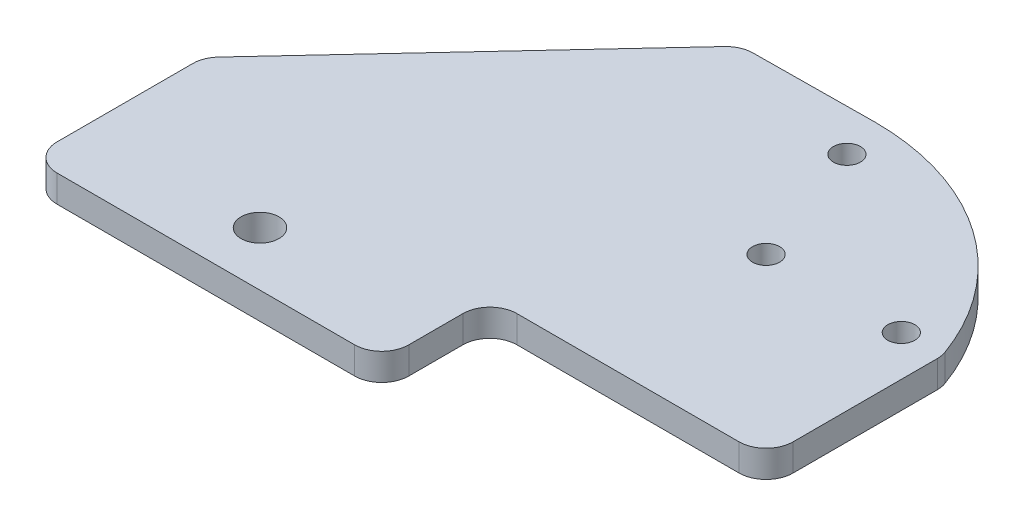
SolidWorks part; units mm, degrees
material "6061 Alloy"
ref_plane "Front Plane" through (0, 0, 0) normal (0, 0, 1) x (1, 0, 0)
ref_plane "Top Plane" through (0, 0, 0) normal (0, 1, 0) x (1, 0, 0)
ref_plane "Right Plane" through (0, 0, 0) normal (1, 0, 0) x (0, 0, -1)
sketch "Sketch1" plane through (0, 0, 0) normal (0, 1, 0) x (1, 0, 0)
  line L2 (5, 0) -> (87.1, 0)
  line L3 (97.1, 10) -> (97.1, 63.2972)
  line L4 (0, 25) -> (97.1, 25) construction
  line L5 (0, 25) -> (-135, 20.1354) construction
  line L6 (-5, -10) -> (-5, -30)
  line L7 (-15, -40) -> (-125, -40)
  line L8 (-135, -30) -> (-135, 20.1354)
  line L9 (-132.3211, 26.9473) -> (-42.1194, 123.8926)
  line L11 (-34.9535, 127.0795) -> (10.0465, 127.5)
  arc A0 (10.0465, 127.5) -> (96.5027, 66.7016) centre (9.8283, 35.3195) cw
  arc A1 (96.5027, 66.7016) -> (97.1, 63.2972) centre (87.1, 63.2972) cw
  arc A2 (87.1, 0) -> (97.1, 10) centre (87.1, 10) ccw
  arc A3 (-5, -10) -> (5, 0) centre (5, -10) cw
  arc A4 (-15, -40) -> (-5, -30) centre (-15, -30) ccw
  arc A5 (-125, -40) -> (-135, -30) centre (-125, -30) cw
  arc A6 (-135, 20.1354) -> (-132.3211, 26.9473) centre (-125, 20.1354) cw
  arc A7 (-42.1194, 123.8926) -> (-34.9535, 127.0795) centre (-34.7983, 117.0808) cw
  point P11 (-38.8619, 126.2179)
  point P14 (-134.3062, 23.7953)
  point P19 (97.1, 65)
  point P23 (97.1, 0)
  point P26 (-5, 0)
  point P29 (-5, -40)
  point P32 (-135, -40)
  point P35 (-135, 24.0681)
  dimension "D1" = 10
  dimension "D7" = 10
  dimension "D9" = 92.1807
  dimension "D2" = 127.5
  dimension "D3" = 45
  dimension "D4" = 65
  dimension "D5" = 25
  dimension "D6" = 45
  dimension "D8" = 140
sketch "Sketch2" plane through (0, 0, 0) normal (0, 1, 0) x (1, 0, 0)
  line L0 (14.999, 111.9846) -> (32.1, 65) construction
  line L1 (32.1, 65) -> (82.1, 65) construction
  line L2 (32.1, 65) -> (42.3606, 36.8092) construction
  line L3 (30.6144, 32.534) -> (54.1068, 41.0845) construction
  line L4 (0, 25) -> (97.1, 25) construction
  circle A0 centre (14.999, 111.9846) radius 5
  circle A1 centre (82.1, 65) radius 5
  circle A2 centre (32.1, 65) radius 5
  point P9 (42.3606, 36.8092)
  dimension "D1" = 50
  dimension "D2" = 50
  dimension "D4" = 110
  dimension "D5" = 7.534
extrude "Boss-Extrude1" add sketch "Sketch1" along normal blind 10
extrude "Cut-Extrude4" cut sketch "Sketch2" against normal through all and the other way through all
sketch "Sketch3" plane through (0, 0, 0) normal (0, -1, 0) x (1, 0, 0)
  line L0 (-125, 40) -> (-15, 40) construction
  line L1 (-70, 20) -> (-135, 20) construction
  line L2 (-135, -20.1354) -> (-135, 30) construction
  line L3 (-70, 20) -> (-5, 20) construction
  line L4 (-5, 30) -> (-5, 10) construction
  circle A0 centre (-70, 20) radius 7
  dimension "D1" = 20
extrude "Cut-Extrude5" cut sketch "Sketch3" against normal through all
